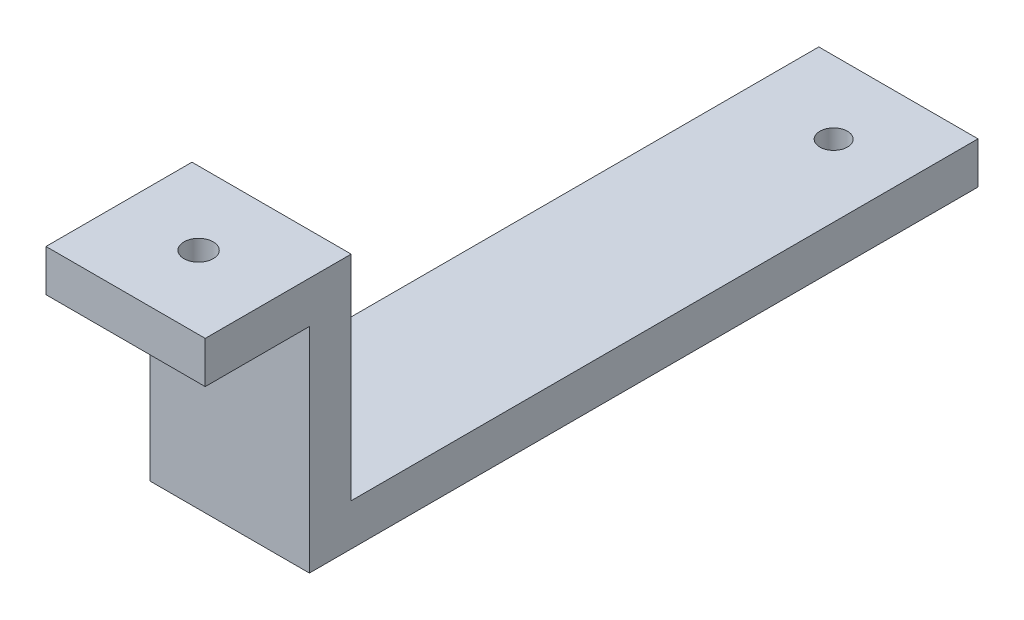
SolidWorks part; units mm, degrees
material "Galvanized Steel"
ref_plane "Front Plane" through (0, 0, 0) normal (0, 0, 1) x (1, 0, 0)
ref_plane "Top Plane" through (0, 0, 0) normal (0, 1, 0) x (1, 0, 0)
ref_plane "Right Plane" through (0, 0, 0) normal (1, 0, 0) x (0, 0, -1)
sketch "Sketch1" plane through (0, 0, 0) normal (1, 0, 0) x (0, 0, -1)
  line L0 (0, 0) -> (34.93, 0)
  line L1 (34.93, 0) -> (34.93, -51.11)
  line L2 (34.93, -51.11) -> (184.93, -51.11)
  dimension "D1" = 34.93
  dimension "D2" = 51.11
extrude "Extrude-Thin1" add sketch "Sketch1" along normal blind 38.1 thin thin type one direction wall 10
sketch "Sketch2" plane through (0, 0, 0) normal (0, 1, 0) x (1, 0, 0)
  line L1 (0, 0) -> (0, 34.93) construction
  circle A0 centre (19.05, 17.465) radius 3.5
  dimension "D1" = 19.05
  dimension "D3" = 7
  dimension "D2" = 17.465
extrude "Cut-Extrude1" cut sketch "Sketch2" against normal through all
sketch "Sketch3" plane through (0, -51.11, 0) normal (0, 1, 0) x (1, 0, 0)
  circle A0 centre (19.05, 174.645) radius 3.5
  dimension "D1" = 7
  dimension "D2" = 157.18
sketch "Sketch4" plane through (0, -51.11, 0) normal (0, 1, 0) x (1, 0, 0)
  circle A0 centre (20.8976, 167.5935) radius 3.3
  dimension "D1" = 6.6
extrude "Cut-Extrude3" cut sketch "Sketch4" against normal blind 60
